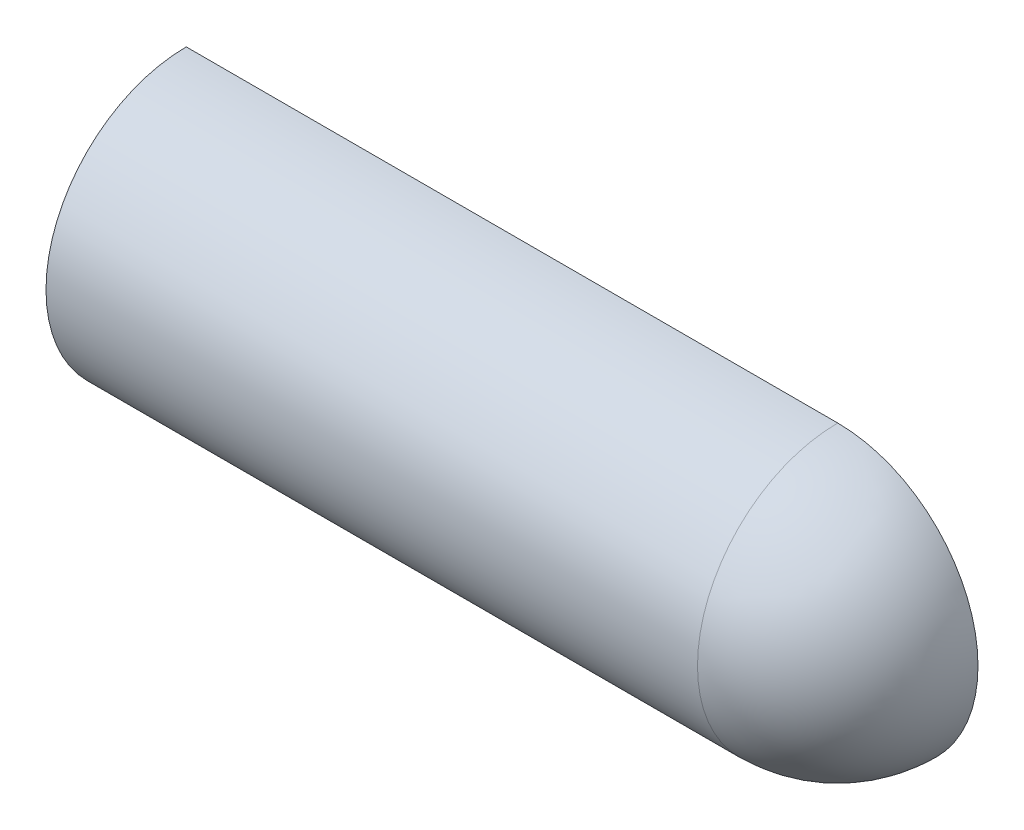
SolidWorks part; units mm, degrees
ref_plane "Front Plane" through (0, 0, 0) normal (0, 0, 1) x (1, 0, 0)
ref_plane "Top Plane" through (0, 0, 0) normal (0, 1, 0) x (1, 0, 0)
ref_plane "Right Plane" through (0, 0, 0) normal (1, 0, 0) x (0, 0, -1)
sketch "Sketch2" plane through (0, 0, 0) normal (0, 0, 1) x (1, 0, 0)
  line L0 (26, 0) -> (31, 0)
  line L2 (-144, 31) -> (0, 31)
  line L3 (-144, 31) -> (-144, 26)
  line L4 (0, 26) -> (-144, 26)
  arc A0 (-2.5128, -30.898) -> (2.5128, 30.898) centre (0, 0) ccw construction
  circle A1 centre (0, 0) radius 31 construction
  arc A3 (31, 0) -> (0, 31) centre (0, 0) ccw
  arc A4 (26, 0) -> (0, 26) centre (0, 0) ccw
revolve "Revolve1" add sketch "Sketch2" angle 180 about L0
